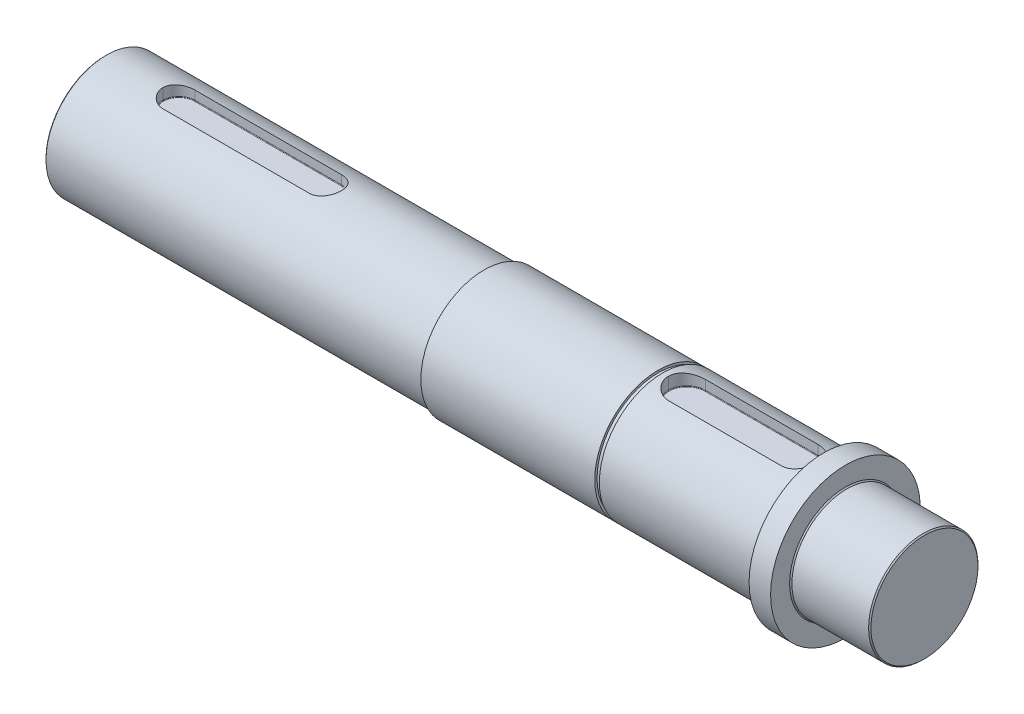
SolidWorks part; units mm, degrees
ref_plane "Piano frontale" through (0, 0, 0) normal (0, 0, 1) x (1, 0, 0)
ref_plane "Piano superiore" through (0, 0, 0) normal (0, 1, 0) x (1, 0, 0)
ref_plane "Piano destro" through (0, 0, 0) normal (1, 0, 0) x (0, 0, -1)
sketch "Schizzo1" plane through (0, 0, 0) normal (0, 0, 1) x (1, 0, 0)
  line L0 (-197.2323, 0) -> (408.6298, 0) construction
  line L1 (0, 0) -> (0, 52.5)
  line L2 (0, 52.5) -> (259, 52.5)
  line L3 (259, 52.5) -> (259, 55)
  line L4 (259, 55) -> (554, 55)
  line L5 (554, 55) -> (554, 65)
  line L6 (554, 65) -> (572.7, 65)
  line L7 (572.7, 65) -> (572.7, 47.5)
  line L8 (572.7, 47.5) -> (628.3, 47.5)
  line L9 (628.3, 47.5) -> (628.3, 0)
  line L10 (628.3, 0) -> (0, 0)
  dimension "D7" = 130
  dimension "D1" = 105
  dimension "D2" = 95
  dimension "D3" = 110
  dimension "D4" = 18.7
  dimension "D5" = 259
  dimension "D6" = 554
  dimension "D8" = 55.6
revolve "Rivoluzione1" add sketch "Schizzo1" angle 360 about L0
chamfer "Smusso1" distance 0.5 angle 45 1 edges at (259, 0, 52.5)
chamfer "Smusso2" distance 1 angle 45 1 edges at (572.7, 0, 47.5)
sketch "Schizzo2" plane through (0, 0, 0) normal (0, 0, 1) x (1, 0, 0)
  line L0 (554, 55) -> (259, 55) construction
  line L1 (419, 62) -> (549, 62)
  line L2 (419, 62) -> (419, 44)
  line L3 (419, 44) -> (549, 44)
  line L4 (549, 62) -> (549, 44)
  line L5 (554, 55) -> (554, -55) construction
  dimension "D1" = 130
  dimension "D2" = 18
  dimension "D3" = 11
  dimension "D4" = 5
extrude "Taglio-Estrusione1" cut sketch "Schizzo2" against normal blind 16 and the other way blind 16
fillet "Raccordo1" radius 0.5 4 edges at (549, 44, 0) (484, 44, 16) (484, 44, -16) (419, 44, 0)
fillet "Raccordo2" radius 16 8 edges at (548.8536, 44.1464, 15.8536) (419.1464, 44.1464, -15.8536) (419.1464, 44.1464, 15.8536) (548.8536, 44.1464, -15.8536) (549, 48.5606, -16) (419, 48.5606, 16) (419, 48.5606, -16) (549, 48.5606, 16)
fillet "Raccordo3" radius 2 1 edges at (554, 0, 55)
sketch "Schizzo3" plane through (0, 0, 0) normal (0, 0, 1) x (1, 0, 0)
  line L0 (554, 65) -> (554, -65) construction
  line L1 (410, 71.3615) -> (414, 71.3615)
  line L2 (410, 71.3615) -> (410, 53)
  line L3 (410, 53) -> (414, 53)
  line L4 (414, 71.3615) -> (414, 53)
  line L5 (-65.3075, 0) -> (690.6013, 0) construction
  dimension "D1" = 4
  dimension "D2" = 53
  dimension "D3" = 140
revolve "Taglia-Rivoluzione1" cut sketch "Schizzo3" angle 360 about L5
sketch "Schizzo6" plane through (0, 0, 0) normal (-1, 0, 0) x (0, 0, 1)
  circle A0 centre (0, 0) radius 52.5
  circle A1 centre (0, 0) radius 52.5 construction
extrude "Estrusione-Estrusione1" add sketch "Schizzo6" along normal blind 70
sketch "Schizzo4" plane through (0, 0, 0) normal (0, 0, 1) x (1, 0, 0)
  line L0 (258.5, 52.5) -> (-70, 52.5) construction
  line L1 (-20, 58.5) -> (135, 58.5)
  line L2 (-20, 58.5) -> (-20, 42.5)
  line L3 (-20, 42.5) -> (135, 42.5)
  line L4 (135, 58.5) -> (135, 42.5)
  line L6 (-70, 52.5) -> (-70, -52.5) construction
  dimension "D1" = 155
  dimension "D2" = 16
  dimension "D3" = 10
  dimension "D4" = 50
extrude "Taglio-Estrusione2" cut sketch "Schizzo4" against normal blind 14 and the other way blind 14
fillet "Raccordo4" radius 14 4 edges at (135, 46.5495, 14) (135, 46.5495, -14) (-20, 46.5495, 14) (-20, 46.5495, -14)
fillet "Raccordo5" radius 0.5 6 edges at (-15.8995, 42.5, 9.8995) (-15.8995, 42.5, -9.8995) (57.5, 42.5, -14) (130.8995, 42.5, -9.8995) (130.8995, 42.5, 9.8995) (57.5, 42.5, 14)
sketch "Schizzo7" plane through (628.3, 0, 0) normal (1, 0, 0) x (0, 0, -1)
  circle A0 centre (0, 0) radius 47.5
  circle A1 centre (0, 0) radius 47.5 construction
extrude "Estrusione-Estrusione2" add sketch "Schizzo7" along normal blind 13
chamfer "Smusso3" distance 1 angle 45 2 edges at (641.3, 0, -47.5) (-70, 0, 52.5)
